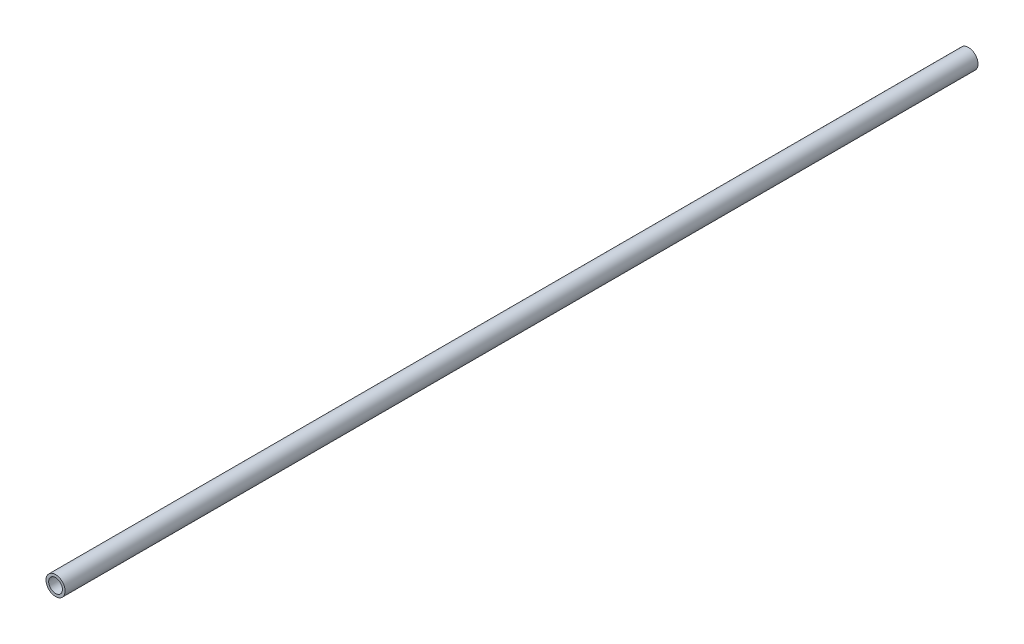
SolidWorks part; units mm, degrees
ref_plane "Front Plane" through (0, 0, 0) normal (0, 0, 1) x (1, 0, 0)
ref_plane "Top Plane" through (0, 0, 0) normal (0, 1, 0) x (1, 0, 0)
ref_plane "Right Plane" through (0, 0, 0) normal (1, 0, 0) x (0, 0, -1)
sketch "Sketch1" plane through (0, 0, 0) normal (0, 0, 1) x (1, 0, 0)
  circle A0 centre (0, 0) radius 2.425
  circle A1 centre (0, 0) radius 1.75
  dimension "D1" = 3.5
  dimension "D2" = 4.85
extrude "Boss-Extrude1" add sketch "Sketch1" along normal blind 232
